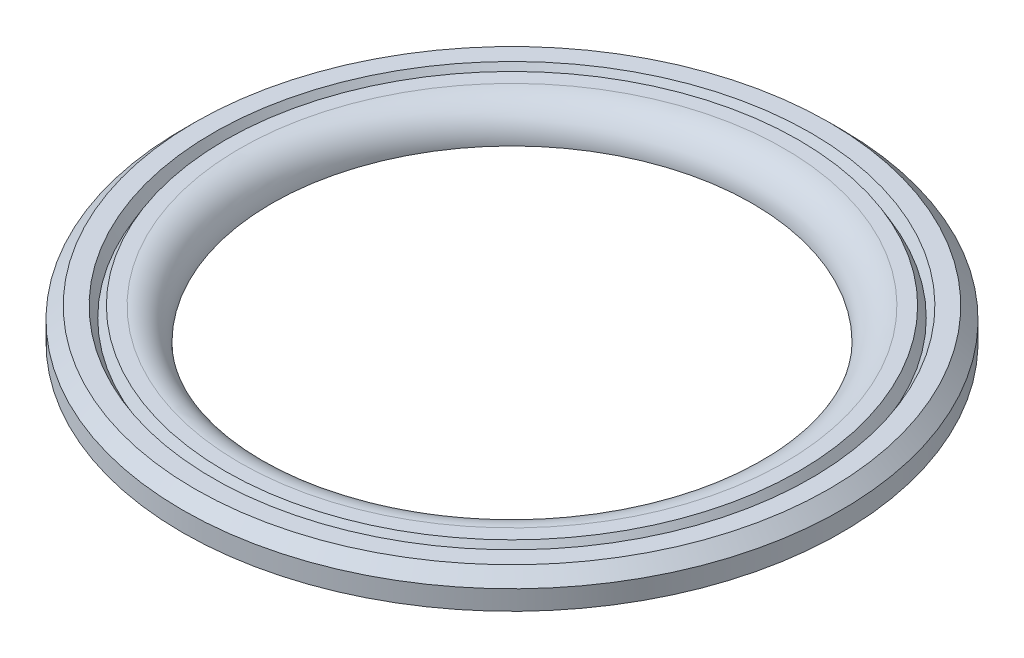
SolidWorks part; units mm, degrees
material "1.4439 (X2CrNiMoN17-13-5)"
ref_plane "Front Plane" through (0, 0, 0) normal (0, 0, 1) x (1, 0, 0)
ref_plane "Top Plane" through (0, 0, 0) normal (0, 1, 0) x (1, 0, 0)
ref_plane "Right Plane" through (0, 0, 0) normal (1, 0, 0) x (0, 0, -1)
sketch "Sketch1" plane through (0, 0, 0) normal (0, 1, 0) x (1, 0, 0)
  circle A0 centre (0, 0) radius 27
  circle A1 centre (0, 0) radius 19.7
  dimension "D1" = 54
  dimension "D2" = 39.4
extrude "Boss-Extrude1" add sketch "Sketch1" along normal blind 2.6
fillet "Fillet1" radius 2.6 1 edges at (0, 2.6, 19.7)
chamfer "Chamfer1" distance 1 angle 45 1 edges at (0, 2.6, 27)
sketch "Sketch2" plane through (0, 0, 0) normal (1, 0, 0) x (0, 0, -1)
  line L0 (24.5, 2.6) -> (24, 1.734)
  line L1 (26, 2.6) -> (-26, 2.6) construction
  line L2 (24, 1.734) -> (23.5, 2.6)
  line L3 (23.5, 2.6) -> (24.5, 2.6)
  line L4 (24, 1.734) -> (24, 3.4904) construction
  dimension "D1" = 30
  dimension "D2" = 30
  dimension "D3" = 1
  dimension "D4" = 24.5
sweep "Cut-Sweep1" cut profiles "Sketch2" path edge at (0, 0, 19.7)
